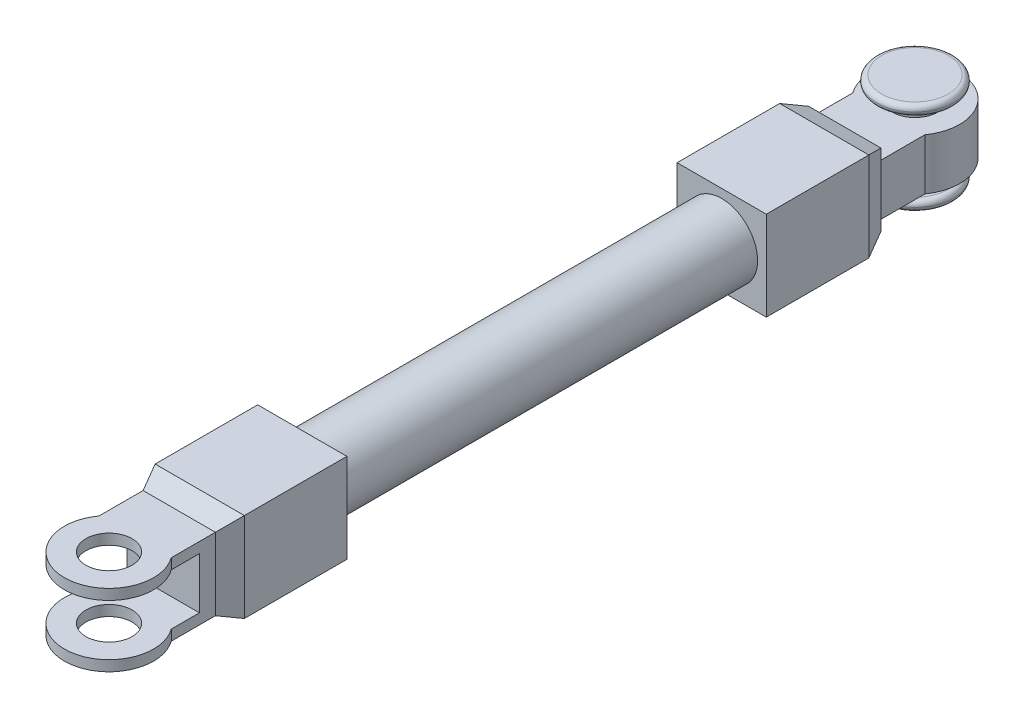
SolidWorks part; units mm, degrees
ref_plane "Front Plane" through (0, 0, 0) normal (0, 0, 1) x (1, 0, 0)
ref_plane "Top Plane" through (0, 0, 0) normal (0, 1, 0) x (1, 0, 0)
ref_plane "Right Plane" through (0, 0, 0) normal (1, 0, 0) x (0, 0, -1)
sketch "Sketch2" plane through (0, 0, 0) normal (0, 0, 1) x (1, 0, 0)
  circle A0 centre (0, 0) radius 70
  dimension "D1" = 140
extrude "Boss-Extrude2" add sketch "Sketch2" against normal blind 1018
sketch "Sketch4" plane through (0, 0, 0) normal (0, 0, 1) x (1, 0, 0)
  line L1 (-87, 87) -> (87, 87)
  line L2 (-87, 87) -> (-87, -87)
  line L3 (-87, -87) -> (87, -87)
  line L4 (87, 87) -> (87, -87)
  line L5 (-87, 87) -> (87, -87) construction
  line L6 (-87, -87) -> (87, 87) construction
  point P0 (0, 0)
  dimension "D1" = 174
  dimension "D2" = 174
extrude "Boss-Extrude3" add sketch "Sketch4" against normal mid plane 200
sketch "Sketch7" plane through (0, 0, -1018) normal (0, 0, -1) x (-1, 0, 0)
  line L1 (-87, 87) -> (87, 87)
  line L2 (-87, 87) -> (-87, -87)
  line L3 (-87, -87) -> (87, -87)
  line L4 (87, 87) -> (87, -87)
  line L5 (-87, 87) -> (87, -87) construction
  line L6 (-87, -87) -> (87, 87) construction
  point P0 (0, 0)
  dimension "D1" = 174
  dimension "D2" = 174
extrude "Boss-Extrude4" add sketch "Sketch7" against normal mid plane 200
ref_plane "Plane1" through (0, 0, 140) normal (0, 0, 1) x (1, 0, 0)
sketch "Sketch8" plane through (0, 0, 140) normal (0, 0, 1) x (1, 0, 0)
  line L1 (-70.5, 70.5) -> (70.5, 70.5)
  line L2 (-70.5, 70.5) -> (-70.5, -70.5)
  line L3 (-70.5, -70.5) -> (70.5, -70.5)
  line L4 (70.5, 70.5) -> (70.5, -70.5)
  line L5 (-70.5, 70.5) -> (70.5, -70.5) construction
  line L6 (-70.5, -70.5) -> (70.5, 70.5) construction
  point P0 (0, 0)
  dimension "D1" = 141
  dimension "D2" = 141
loft "Loft1" add profiles "Sketch8" section face at (0, 0, 100) section "Sketch8" connector at (87, 87, 100) connector at (70.5, 70.5, 140)
ref_plane "Plane2" through (0, 0, -160) normal (0, 0, -1) x (-1, 0, 0)
sketch "Sketch9" plane through (0, 0, -160) normal (0, 0, -1) x (-1, 0, 0)
  line L5 (-71.5, 71.5) -> (71.5, 71.5)
  line L6 (-71.5, 71.5) -> (-71.5, -71.5)
  line L7 (-71.5, -71.5) -> (71.5, -71.5)
  line L8 (71.5, 71.5) -> (71.5, -71.5)
  line L9 (-71.5, 71.5) -> (71.5, -71.5) construction
  line L10 (-71.5, -71.5) -> (71.5, 71.5) construction
  point P0 (0, 0)
  point P1 (0, 0)
  dimension "D1" = 143
  dimension "D2" = 143
ref_plane "Plane3" through (0, 0, -1158) normal (0, 0, -1) x (-1, 0, 0)
sketch "Sketch10" plane through (0, 0, -1158) normal (0, 0, -1) x (-1, 0, 0)
  line L0 (-71.5, 71.5) -> (71.5, -71.5) construction
  line L1 (-70.5, 70.5) -> (70.5, 70.5)
  line L2 (-70.5, 70.5) -> (-70.5, -70.5)
  line L3 (-70.5, -70.5) -> (70.5, -70.5)
  line L4 (70.5, 70.5) -> (70.5, -70.5)
  line L5 (-70.5, 70.5) -> (70.5, -70.5) construction
  line L6 (-70.5, -70.5) -> (70.5, 70.5) construction
  point P0 (0, 0)
  dimension "D1" = 141
  dimension "D2" = 141
loft "Loft8" add profiles "Sketch10" section face at (0, 0, -1118) section "Sketch10" connector at (-87, 87, -1118) connector at (-70.5, 70.5, -1158)
ref_plane "Plane4" through (0, 70.5, 0) normal (0, 1, 0) x (-1, 0, 0)
sketch "Sketch14" plane through (0, 70.5, 0) normal (0, 1, 0) x (-1, 0, 0)
  line L0 (94.8419, 140) -> (-94.8419, 140) construction
  circle A0 centre (0, 277) radius 87
  dimension "D1" = 174
  dimension "D2" = 137
extrude "Boss-Extrude5" add sketch "Sketch14" against normal blind 141 separate body contours A0
sketch "Sketch16" plane through (0, 70.5, 0) normal (0, 1, 0) x (1, 0, 0)
  circle A0 centre (0, -277) radius 45
  dimension "D1" = 90
extrude "Cut-Extrude1" cut sketch "Sketch16" against normal up to next (141 mm away)
sketch "Sketch17" plane through (0, 0, 140) normal (0, 0, 1) x (1, 0, 0)
  line L1 (-70.5, 70.5) -> (70.5, 70.5)
  line L2 (-70.5, 70.5) -> (-70.5, -70.5)
  line L3 (-70.5, -70.5) -> (70.5, -70.5)
  line L4 (70.5, 70.5) -> (70.5, -70.5)
  line L5 (-70.5, 70.5) -> (70.5, -70.5) construction
  line L6 (-70.5, -70.5) -> (70.5, 70.5) construction
  point P0 (0, 0)
  dimension "D1" = 141
  dimension "D2" = 141
extrude "Boss-Extrude6" add sketch "Sketch17" along normal up to next
ref_plane "Plane6" through (-94.5, 0, 0) normal (-1, 0, 0) x (0, 0, 1)
sketch "Sketch23" plane through (-94.5, 0, 0) normal (-1, 0, 0) x (0, 0, 1)
  line L0 (226.0221, -70.5) -> (364, -70.5) construction
  line L1 (171.1765, -50) -> (367.3984, -50)
  line L2 (171.1765, -50) -> (171.1765, 50)
  line L3 (171.1765, 50) -> (367.3984, 50)
  line L4 (367.3984, -50) -> (367.3984, 50)
  dimension "D1" = 100
  dimension "D2" = 20.5
extrude "Cut-Extrude2" cut sketch "Sketch23" against normal blind 201
sketch "Sketch24" plane through (0, 0, 0) normal (0, 1, 0) x (1, 0, 0)
  line L0 (-70.5, 1158) -> (70.5, 1158) construction
  line L2 (-70.5, 1158) -> (70.5, 1158)
  line L3 (-70.5, 1158) -> (-70.5, 1244.0221)
  line L5 (70.5, 1158) -> (70.5, 1244.0221)
  arc A0 (70.5, 1244.0221) -> (-70.5, 1244.0221) centre (0, 1295) ccw
  point P4 (0, 1158)
  dimension "D1" = 174
  dimension "D2" = 137
  dimension "D3" = 141
extrude "Boss-Extrude7" add sketch "Sketch24" along normal mid plane 100 separate body
sketch "Sketch26" plane through (0, 50, 0) normal (0, 1, 0) x (1, 0, 0)
  circle A0 centre (0, 1295) radius 45
  dimension "D1" = 90
extrude "Boss-Extrude8" add sketch "Sketch26" along normal blind 20.5
sketch "Sketch27" plane through (0, -50, 0) normal (0, -1, 0) x (1, 0, 0)
  circle A0 centre (0, -1295) radius 45
  dimension "D1" = 90
extrude "Boss-Extrude9" add sketch "Sketch27" along normal blind 20.5
sketch "Sketch28" plane through (0, -70.5, 0) normal (0, -1, 0) x (1, 0, 0)
  circle A0 centre (0, -1295) radius 75
  dimension "D1" = 150
extrude "Boss-Extrude10" add sketch "Sketch28" along normal blind 20
fillet "Fillet1" radius 10 2 edges at (0, -70.5, -1370) (0, -90.5, -1370)
sketch "Sketch29" plane through (0, 70.5, 0) normal (0, 1, 0) x (1, 0, 0)
  circle A0 centre (0, 1295) radius 75
  dimension "D1" = 150
extrude "Boss-Extrude11" add sketch "Sketch29" along normal blind 20
fillet "Fillet2" radius 10 2 edges at (0, 70.5, -1220) (0, 90.5, -1220)
